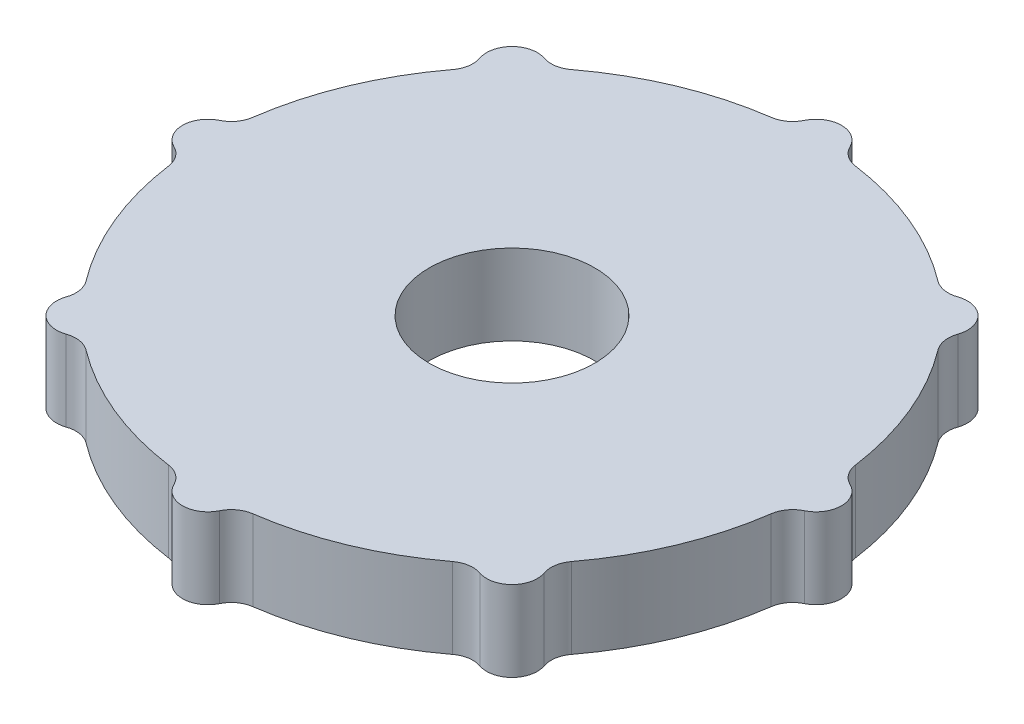
SolidWorks part; units mm, degrees
ref_plane "Front Plane" through (0, 0, 0) normal (1, 0, 0) x (0, 1, 0)
ref_plane "Top Plane" through (0, 0, 0) normal (0, 0, 1) x (0, 1, 0)
ref_plane "Right Plane" through (0, 0, 0) normal (0, 1, 0) x (-1, 0, 0)
sketch "Sketch2" plane through (0, 0, 0) normal (0, 1, 0) x (-1, 0, 0)
  line L0 (0, 0) -> (0, 12) construction
  circle A0 centre (0, 0) radius 12
  arc A1 (-0.8992, 12.4375) -> (0.8992, 12.4375) centre (0, 12) cw
  arc A2 (-0.8992, 12.4375) -> (-1.6601, 11.8846) centre (-1.7984, 12.875) cw
  arc A3 (0.8992, 12.4375) -> (1.6601, 11.8846) centre (1.7984, 12.875) ccw
  circle A10 centre (0, 0) radius 3.2639
  point P15 (0, 13)
  point P28 (0, 0)
  dimension "D1" = 12
  dimension "D3" = 1
  dimension "D4" = 1
  dimension "D6" = 6.5278
  dimension "D2" = 13
extrude "Boss-Extrude1" add sketch "Sketch2" along normal blind 3.175 contours A0 A10 region at (7.6537, 0, -8.7971)
extrude "Boss-Extrude2" add sketch "Sketch2<3>" along normal blind 3.175 contours A3 A1 A2 A0 region at (0, 0, 12.3881)
sketch "Sketch2<3>" plane through (0, 0, 0) normal (0, 1, 0) x (-1, 0, 0) same geometry as "Sketch2"
pattern_circular "CirPattern1" count 8 over 360 about axis through (0, 3.175, 0) along (0, -1, 0) of "Boss-Extrude2"
